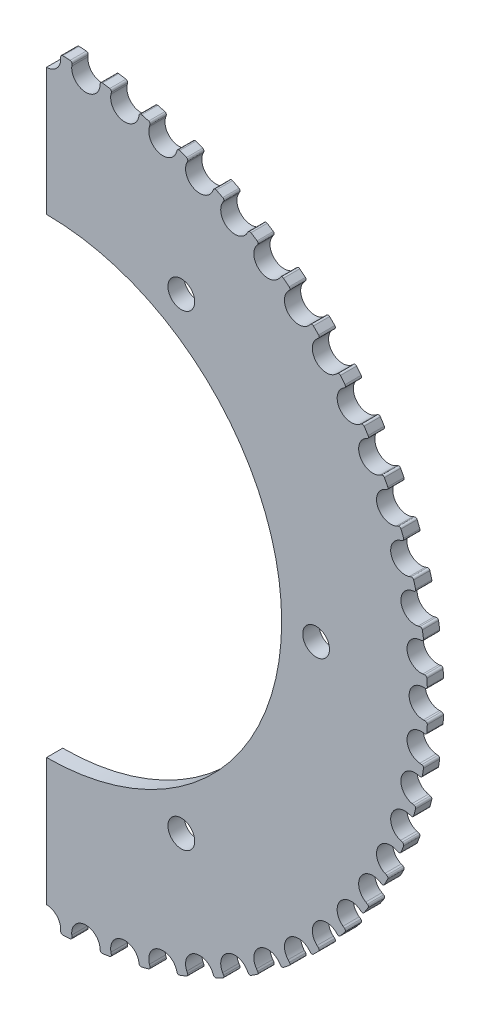
SolidWorks part; units mm, degrees
material "6061 Alloy"
ref_plane "Front Plane" through (0, 0, 0) normal (0, 0, 1) x (1, 0, 0)
ref_plane "Top Plane" through (0, 0, 0) normal (0, 1, 0) x (1, 0, 0)
ref_plane "Right Plane" through (0, 0, 0) normal (1, 0, 0) x (0, 0, -1)
sketch "Sketch1" plane through (0, 0, 0) normal (0, 0, 1) x (1, 0, 0)
  circle A0 centre (0, 0) radius 94
  circle A1 centre (0, 0) radius 58
  dimension "D1" = 188
  dimension "D2" = 116
extrude "Boss-Extrude1" add sketch "Sketch1" along normal blind 4
sketch "Sketch2" plane through (0, 0, 0) normal (0, 0, 1) x (1, 0, 0)
  line L0 (-3.5, 92.9348) -> (-3.5, 93.9348)
  line L1 (3.5, 92.9348) -> (3.5, 93.9348)
  arc A0 (-3.5, 92.9348) -> (3.5, 92.9348) centre (0, 92.9348) ccw
  circle A2 centre (0, 0) radius 94 construction
  arc A3 (3.5, 93.9348) -> (-3.5, 93.9348) centre (0, 0) ccw
  dimension "D1" = 7
  dimension "D2" = 1
extrude "Cut-Extrude1" cut sketch "Sketch2" against normal through all both and the other way through all
fillet "Fillet1" radius 0.5 2 edges at (3.5, 93.9348, 2) (-3.5, 93.9348, 2)
pattern_circular "CirPattern1" count 60 over 360 about axis through (0, 0, 4) along (0, 0, -1) of "Cut-Extrude1", "Fillet1" reverse direction yes
sketch "Sketch3" plane through (0, 0, 4) normal (0, 0, 1) x (1, 0, 0)
  circle A0 centre (0, 0) radius 66.5 construction
  point P5 (66.5, 0)
  dimension "D1" = 133
hole_wizard "M6 Clearance Hole1" positions "Sketch3" profile "Sketch4" hole size "M6" standard "ANSI Metric" end condition up to next
sketch "Sketch4" plane through (66.5, 0, 4) normal (1, 0, 0) x (0, -1, 0)
  line L0 (0, 0) -> (0, 4)
  line L1 (0, 4) -> (3.3, 4)
  line L2 (3.3, 4) -> (3.3, 0)
  line L5 (3.3, 0) -> (0, 0)
  line L11 (0, -6.35) -> (0, 107.95) construction
  dimension "Thru Hole Dia." = 6.6
  dimension "Thru Hole Depth" = 4
pattern_circular "CirPattern2" count 6 over 360 about axis through (0, 0, 4) along (0, 0, -1) of "M6 Clearance Hole1" reverse direction yes
sketch "Sketch5" plane through (0, 0, 0) normal (0, 0, 1) x (1, 0, 0)
  line L0 (0, 125.0582) -> (0, -117.4481)
extrude "Cut-Extrude2" cut sketch "Sketch5" against normal through all both and the other way through all flip side to cut
